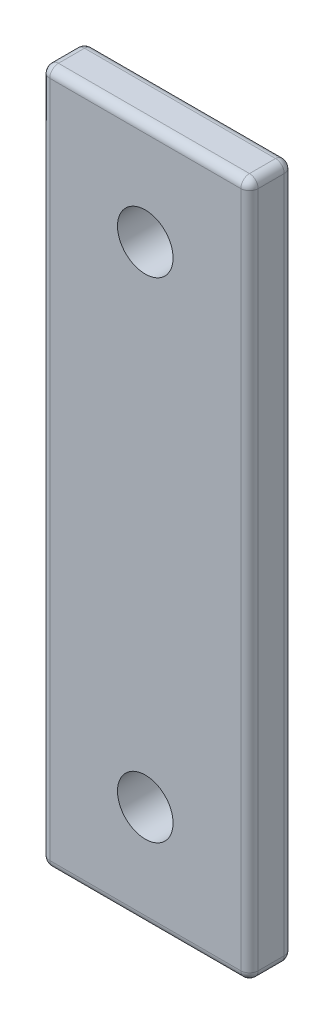
SolidWorks part; units mm, degrees
ref_plane "Front Plane" through (0, 0, 0) normal (0, 0, 1) x (1, 0, 0)
ref_plane "Top Plane" through (0, 0, 0) normal (0, 1, 0) x (1, 0, 0)
ref_plane "Right Plane" through (0, 0, 0) normal (1, 0, 0) x (0, 0, -1)
sketch "Sketch1" plane through (0, 0, 0) normal (0, 0, 1) x (1, 0, 0)
  line L1 (-24, -80) -> (24, -80)
  line L2 (-24, -80) -> (-24, 80)
  line L3 (-24, 80) -> (24, 80)
  line L4 (24, -80) -> (24, 80)
  line L5 (-24, -80) -> (24, 80) construction
  line L6 (-24, 80) -> (24, -80) construction
  point P0 (0, 0)
  dimension "D1" = 48
  dimension "D2" = 160
extrude "Boss-Extrude1" add sketch "Sketch1" along normal blind 10
fillet "Fillet1" radius 2 8 edges at (0, -80, 10) (-24, 0, 10) (0, 80, 10) (24, 0, 10) (0, 80, 0) (-24, 0, 0) (0, -80, 0) (24, 0, 0)
fillet "Fillet2" radius 2 12 edges at (23.4142, 79.4142, 9.4142) (23.4142, 79.4142, 0.5858) (23.4142, -79.4142, 9.4142) (23.4142, -79.4142, 0.5858) (-23.4142, -79.4142, 9.4142) (-23.4142, -79.4142, 0.5858) (-23.4142, 79.4142, 9.4142) (-23.4142, 79.4142, 0.5858) (24, 80, 5) (24, -80, 5) (-24, -80, 5) (-24, 80, 5)
sketch "Sketch2" plane through (0, 0, 0) normal (0, 0, -1) x (-1, 0, 0)
  line L0 (22, 78) -> (-22, 78) construction
  circle A0 centre (0, 56.35) radius 6.4
  dimension "D1" = 12.8
  dimension "D2" = 21.65
extrude "Cut-Extrude1" cut sketch "Sketch2" against normal through all
sketch "Sketch6" plane through (0, 0, 0) normal (0, 0, -1) x (-1, 0, 0)
  line L0 (-22, 0) -> (22, 0) construction
  line L1 (-22, 78) -> (-22, -78) construction
  line L2 (22, -78) -> (22, 78) construction
mirror "Mirror2" about plane through (0, 0, 0) normal (0, 1, 0) of "Cut-Extrude1"
